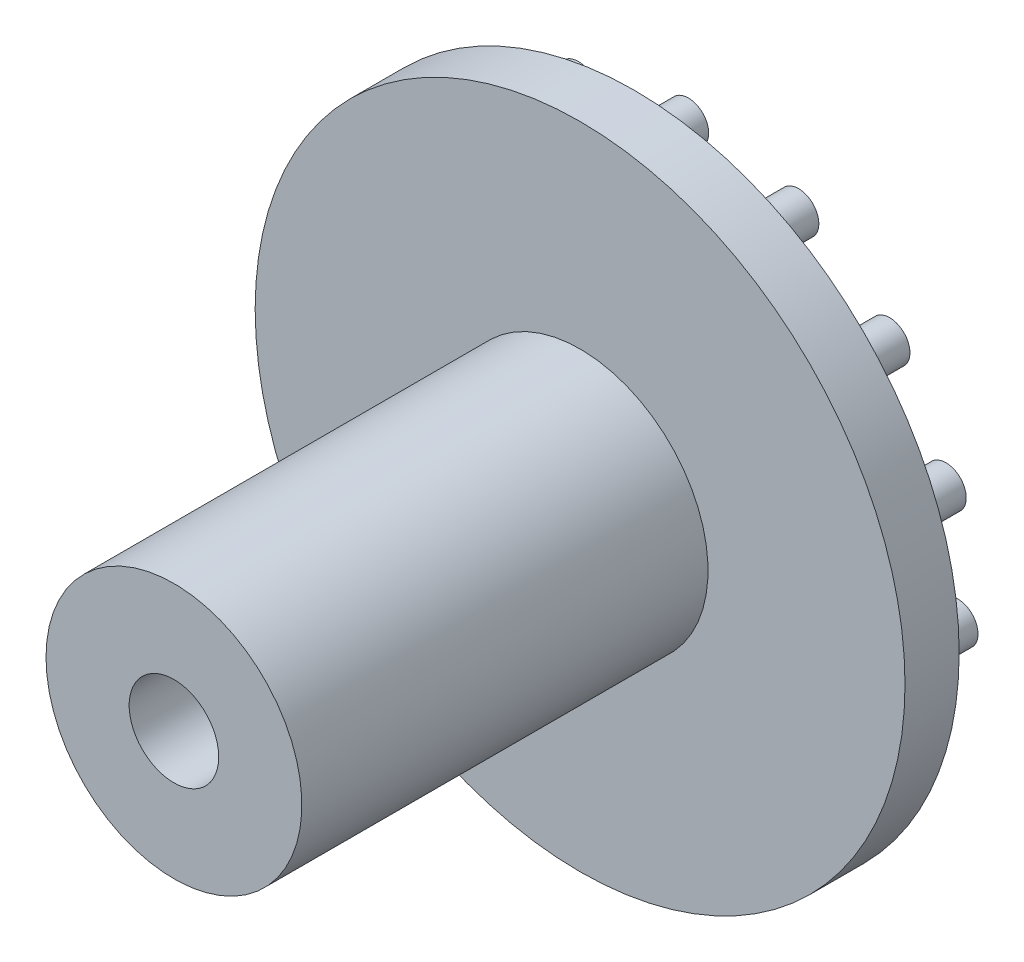
SolidWorks part; units mm, degrees
material "ABS"
ref_plane "Front Plane" through (0, 0, 0) normal (0, 0, 1) x (1, 0, 0)
ref_plane "Top Plane" through (0, 0, 0) normal (0, 1, 0) x (1, 0, 0)
ref_plane "Right Plane" through (0, 0, 0) normal (1, 0, 0) x (0, 0, -1)
sketch "Sketch1" plane through (0, 0, 0) normal (0, 0, 1) x (1, 0, 0)
  circle A0 centre (0, 0) radius 4.55
  circle A1 centre (0, 0) radius 15.24
  dimension "D1" = 9.1
  dimension "D2" = 30.48
extrude "Boss-Extrude1" add sketch "Sketch1" along normal blind 2.54
sketch "Sketch2" plane through (0, 0, 2.54) normal (0, 0, 1) x (1, 0, 0)
  circle A0 centre (0, 0) radius 6
  dimension "D1" = 12
extrude "Boss-Extrude2" add sketch "Sketch2" along normal blind 19.05
sketch "Sketch3" plane through (0, 0, 21.59) normal (0, 0, 1) x (1, 0, 0)
  line L1 (3.6662, 6.35) -> (-3.6662, 6.35)
  line L2 (-3.6662, 6.35) -> (-7.3323, 0)
  line L3 (-7.3323, 0) -> (-3.6662, -6.35)
  line L4 (-3.6662, -6.35) -> (3.6662, -6.35)
  line L5 (3.6662, -6.35) -> (7.3323, 0)
  line L6 (7.3323, 0) -> (3.6662, 6.35)
  circle A1 centre (0, 0) radius 6.35 construction
  dimension "D1" = 12.7
extrude "Boss-Extrude3" [suppressed] add sketch "Sketch3" along normal blind 38.1
sketch "Sketch4" [suppressed] plane through (0, 0, 47.64) normal (0, 0, 1) x (1, 0, 0)
  line L1 (-0.635, 1.905) -> (0.635, 1.905)
  line L2 (-0.635, 1.905) -> (-0.635, 4.445)
  line L3 (-0.635, 4.445) -> (0.635, 4.445)
  line L4 (0.635, 1.905) -> (0.635, 4.445)
  point P4 (0, 1.905)
  dimension "D1" = 2.54
  dimension "D2" = 1.905
  dimension "D3" = 1.27
extrude "Boss-Extrude4" [suppressed] add sketch "Sketch4" against normal blind 2.54
sketch "Sketch5" plane through (0, 0, 0) normal (0, 0, -1) x (-1, 0, 0)
  line L0 (0, 0) -> (0, 12.7) construction
  circle A0 centre (0, 12.7) radius 0.9525
  circle A13 centre (5.1656, 11.602) radius 0.9525
  circle A14 centre (9.4379, 8.498) radius 0.9525
  circle A15 centre (12.0784, 3.9245) radius 0.9525
  circle A16 centre (12.6304, -1.3275) radius 0.9525
  circle A17 centre (10.9985, -6.35) radius 0.9525
  circle A18 centre (7.4649, -10.2745) radius 0.9525
  circle A19 centre (2.6405, -12.4225) radius 0.9525
  circle A20 centre (-2.6405, -12.4225) radius 0.9525
  circle A21 centre (-7.4649, -10.2745) radius 0.9525
  circle A22 centre (-10.9985, -6.35) radius 0.9525
  circle A23 centre (-12.6304, -1.3275) radius 0.9525
  circle A24 centre (-12.0784, 3.9245) radius 0.9525
  circle A25 centre (-9.4379, 8.498) radius 0.9525
  circle A26 centre (-5.1656, 11.602) radius 0.9525
  dimension "D2" = 1.905
  dimension "D1" = 12.7
  dimension "D3" = 15
  dimension "D4" = 12.7
extrude "Boss-Extrude5" add sketch "Sketch5" along normal blind 2.54
sketch "Sketch6" plane through (0, 0, 21.59) normal (0, 0, 1) x (1, 0, 0)
  circle A1 centre (0, 0) radius 6
  circle A2 centre (0, 0) radius 6
  point P1 (0, 0)
  dimension "D1" = 0
hole_wizard "M5x0.8 Tapped Hole2" positions "Sketch6" profile "Sketch7" tap size "M5x0.8" standard "ANSI Metric" end condition through all
cosmetic thread "Hole Thread1" parameters "D2"=5
sketch "Sketch7" plane through (0, 0, 21.59) normal (1, 0, 0) x (0, -1, 0)
  line L0 (0, 0) -> (0, 24.13)
  line L1 (0, 24.13) -> (2.1, 24.13)
  line L2 (2.1, 24.13) -> (2.1, 0)
  line L5 (2.1, 0) -> (0, 0)
  line L11 (0, -6.35) -> (0, 107.95) construction
  dimension "Thru Tap Drill Dia." = 4.2
  dimension "Thru Tap Drill Depth" = 24.13
